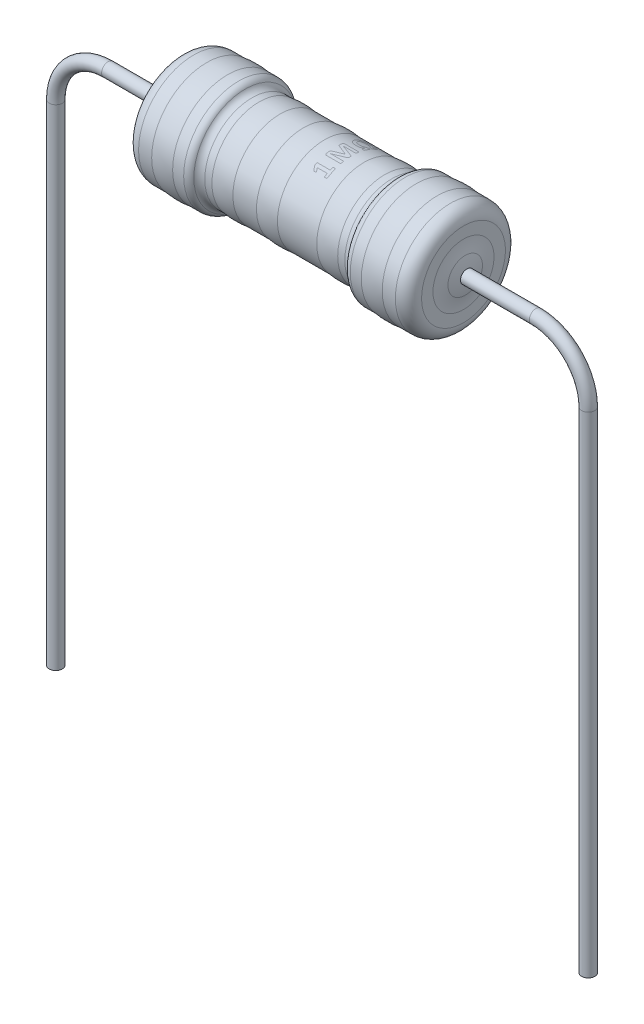
SolidWorks part; units mm, degrees
ref_plane "Front Plane" through (0, 0, 0) normal (0, 0, 1) x (1, 0, 0)
ref_plane "Top Plane" through (0, 0, 0) normal (0, 1, 0) x (1, 0, 0)
ref_plane "Right Plane" through (0, 0, 0) normal (1, 0, 0) x (0, 0, -1)
sketch "Sketch Set Wire Width" plane through (0, 0, 0) normal (0, 0, 1) x (1, 0, 0)
  line L0 (-8.16, 0) -> (8.16, 0)
  line L1 (-10.16, -2) -> (-10.16, -20.6984)
  line L2 (10.16, -2) -> (10.16, -20.6984)
  line L3 (-10.16, -20.6984) -> (10.16, -20.6984) construction
  line L4 (0, 0) -> (0, -20.6984) construction
  arc A0 (-8.16, 0) -> (-10.16, -2) centre (-8.16, -2) ccw
  arc A1 (8.16, 0) -> (10.16, -2) centre (8.16, -2) cw
  dimension "D2" = 2
  dimension "D3" = 60
  dimension "D1" = 20.32
sketch "Sketch Wire Diameter" plane through (0, 0, 0) normal (1, 0, 0) x (0, 0, -1)
  circle A0 centre (0, 0) radius 0.25
  dimension "D1" = 0.5
sweep "SET WIRE LENGTH" add profiles "Sketch Wire Diameter" path "Sketch Set Wire Width"
sketch "Sketch3" plane through (0, 0, 0) normal (0, 0, 1) x (1, 0, 0)
  line L0 (-5.4, 0) -> (5.4, 0)
  line L1 (0, 0) -> (0, 1.8) construction
  line L2 (-2.9, 1.8) -> (2.9, 1.8)
  line L3 (-5.4, 0) -> (-5.4, 1.6)
  line L4 (-4.9, 2.1) -> (-3.18, 2.1)
  line L5 (-2.9, 1.82) -> (-2.9, 1.8)
  line L6 (5.4, 0) -> (5.4, 1.6)
  line L7 (4.9, 2.1) -> (3.18, 2.1)
  line L8 (2.9, 1.82) -> (2.9, 1.8)
  arc A0 (-5.4, 1.6) -> (-4.9, 2.1) centre (-4.9, 1.6) cw
  arc A1 (5.4, 1.6) -> (4.9, 2.1) centre (4.9, 1.6) ccw
  arc A2 (-3.18, 2.1) -> (-2.9, 1.82) centre (-3.18, 1.82) cw
  arc A3 (3.18, 2.1) -> (2.9, 1.82) centre (3.18, 1.82) ccw
  dimension "D5" = 0.5
  dimension "D6" = 0.28
  dimension "D1" = 10.8
  dimension "D2" = 5.8
  dimension "D3" = 1.8
  dimension "D4" = 2.1
revolve "Revolve2" add sketch "Sketch3" angle 360 about L0
fillet "Fillet1" radius 0.3 2 edges at (2.9, 0, 1.8) (-2.9, 0, 1.8)
sketch "Sketch5" plane through (0, 0, 0) normal (0, 0, 1) x (1, 0, 0)
  line L0 (0, 0) -> (2, 0) construction
  line L1 (0, 0) -> (-0.3, 0) construction
  line L2 (-0.3, 0) -> (-2, 0) construction
  line L3 (-2, 0) -> (-4, 0) construction
  line L4 (2, 0) -> (4, 0) construction
  line L5 (-4, 0) -> (-4, 2.1) construction
  line L6 (-0.3, 0) -> (-0.3, 1.8) construction
  line L7 (-2, 0) -> (-2, 1.8) construction
  line L8 (2, 0) -> (2, 1.8) construction
  line L9 (4, 0) -> (4, 2.1) construction
  line L10 (-4, 2.1) -> (-4, 2.13) construction
  line L11 (-4.9, 2.1) -> (-3.18, 2.1) construction
  line L12 (4.9, 2.1) -> (3.18, 2.1) construction
  line L13 (-2.9, 1.8) -> (2.9, 1.8) construction
  line L14 (-2, 1.8) -> (-2, 1.83) construction
  line L17 (-4.4, 2.1) -> (-3.6, 2.1)
  line L19 (-5.4, 0) -> (5.4, 0) construction
  line L22 (-2.4, 1.8) -> (-1.6, 1.8) construction
  line L26 (-0.7, 1.8) -> (0.1, 1.8) construction
  line L30 (1.6, 1.8) -> (2.4, 1.8) construction
  line L34 (3.6, 2.1) -> (4.4, 2.1) construction
  line L36 (-0.3, 1.8) -> (-0.3, 1.83) construction
  line L37 (2, 1.8) -> (2, 1.83) construction
  line L38 (4, 2.1) -> (4, 2.13) construction
  arc A0 (-4.4, 2.1) -> (-3.6, 2.1) centre (-4, -0.5517) cw
  arc A1 (-2.4, 1.8) -> (-1.6, 1.8) centre (-2, -0.8517) cw construction
  arc A2 (-0.7, 1.8) -> (0.1, 1.8) centre (-0.3, -0.8517) cw construction
  arc A3 (1.6, 1.8) -> (2.4, 1.8) centre (2, -0.8517) cw construction
  arc A4 (3.6, 2.1) -> (4.4, 2.1) centre (4, -0.5517) cw construction
  dimension "D3" = 0.8
  dimension "D1" = 4
  dimension "D2" = 4
  dimension "D4" = 0.03
  dimension "D5" = 2
  dimension "D6" = 2
  dimension "D7" = 1.7
revolve "Band 1" add sketch "Sketch5" angle 360 about L2
sketch "Sketch8" plane through (0, 0, 0) normal (0, 0, 1) x (1, 0, 0)
  line L0 (-2.4, 1.8) -> (-1.6, 1.8) construction
  line L1 (-2.4, 1.8) -> (-1.6, 1.8)
  arc A0 (-1.6, 1.8) -> (-2.4, 1.8) centre (-2, -0.8517) ccw construction
  arc A1 (-1.6, 1.8) -> (-2.4, 1.8) centre (-2, -0.8517) ccw
revolve "Band 2" add sketch "Sketch8" angle 360 about L2
sketch "Sketch9" plane through (0, 0, 0) normal (0, 0, 1) x (1, 0, 0)
  line L0 (-0.7, 1.8) -> (0.1, 1.8) construction
  line L1 (-0.7, 1.8) -> (0.1, 1.8)
  arc A0 (0.1, 1.8) -> (-0.7, 1.8) centre (-0.3, -0.8517) ccw construction
  arc A1 (0.1, 1.8) -> (-0.7, 1.8) centre (-0.3, -0.8517) ccw
revolve "Band 3" add sketch "Sketch9" angle 360 about L2
sketch "Sketch10" plane through (0, 0, 0) normal (0, 0, 1) x (1, 0, 0)
  line L0 (1.6, 1.8) -> (2.4, 1.8) construction
  line L1 (1.6, 1.8) -> (2.4, 1.8)
  arc A0 (2.4, 1.8) -> (1.6, 1.8) centre (2, -0.8517) ccw construction
  arc A1 (2.4, 1.8) -> (1.6, 1.8) centre (2, -0.8517) ccw
revolve "Band 4" add sketch "Sketch10" angle 360 about L0
sketch "Sketch11" plane through (0, 0, 0) normal (0, 0, 1) x (1, 0, 0)
  line L0 (3.6, 2.1) -> (4.4, 2.1) construction
  line L1 (3.6, 2.1) -> (4.4, 2.1)
  arc A0 (4.4, 2.1) -> (3.6, 2.1) centre (4, -0.5517) ccw construction
  arc A1 (4.4, 2.1) -> (3.6, 2.1) centre (4, -0.5517) ccw
revolve "Band 5" add sketch "Sketch11" angle 360 about L4
sketch "Sketch12" plane through (0, 0, 0) normal (0, 0, 1) x (1, 0, 0)
  line L0 (-5.35, 0) -> (5.35, 0) construction
  line L1 (-5.35, 1) -> (-5.35, 0)
  line L2 (5.35, 1) -> (5.35, 0)
  line L3 (-5.35, 0) -> (-5.55, 0)
  line L4 (5.35, 0) -> (5.55, 0)
  arc A0 (-5.35, 1) -> (-5.55, 0) centre (-2.95, 0) ccw
  arc A1 (5.35, 1) -> (5.55, 0) centre (2.95, 0) cw
  dimension "D3" = 0.2
  dimension "D4" = 2.6
  dimension "D1" = 10.7
  dimension "D2" = 1
revolve "Revolve10" add sketch "Sketch12" angle 360 about L0
fillet "Fillet2" radius 2 2 edges at (5.4, 0, 0.8703) (-5.4, 0, -0.8703)
ref_plane "Plane2" through (0, 3, 0) normal (0, 1, 0) x (1, 0, 0)
sketch "Sketch13" plane through (0, 3, 0) normal (0, 1, 0) x (1, 0, 0)
  line L0 (0, 0) -> (1.15, 0) construction
  line L1 (1.15, 1.75) -> (1.15, -1.75) construction
  text T0 "1MΩ" font "Calibri" height 0.6
  dimension "D1" = 3.5
  dimension "D2" = 1.15
wrap "Wrap1" sketch "Sketch13" wrap type scribe source sketch "Sketch13" face at (0.1, 1.8, 0)
